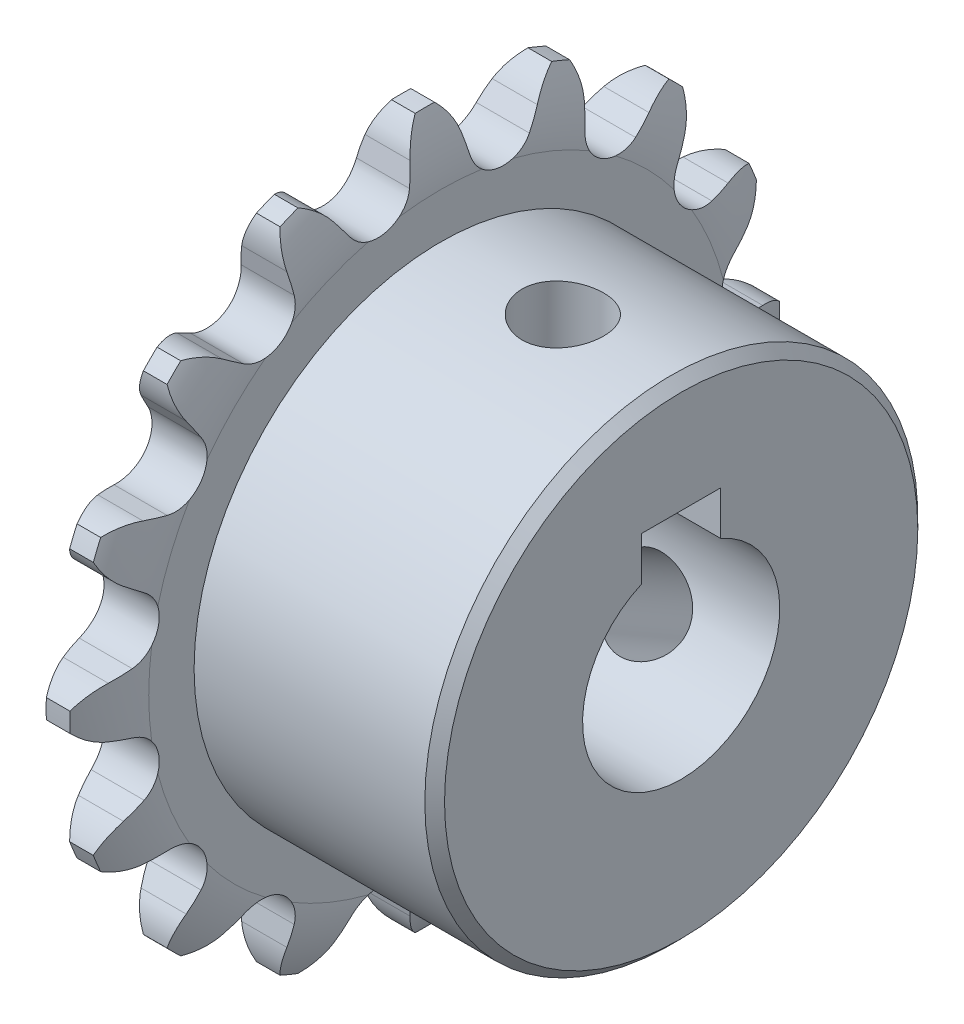
SolidWorks part; units mm, degrees
ref_plane "Front Plane" through (0, 0, 0) normal (0, 0, 1) x (1, 0, 0)
ref_plane "Top Plane" through (0, 0, 0) normal (0, 1, 0) x (1, 0, 0)
ref_plane "Right Plane" through (0, 0, 0) normal (1, 0, 0) x (0, 0, -1)
ref_axis "Axis_X" through (-0.8516, 0, 0) along (1, 0, 0)
ref_axis "Axis_Y" through (0, 19.8, 0) along (0, -1, 0)
ref_axis "Axis_Z" through (0, 0, -19.8) along (0, 0, 1)
sketch "Sketch1" plane through (0, 0, 0) normal (0, 0, 1) x (1, 0, 0)
  line L0 (0, 0) -> (15, 0) construction
  line L1 (0, 5) -> (0, 18)
  line L2 (0, 18) -> (2.8, 18)
  line L3 (2.8, 18) -> (2.8, 12.5)
  line L4 (2.8, 12.5) -> (15, 12.5)
  line L5 (15, 12.5) -> (15, 5)
  line L7 (0, 5) -> (15, 5)
  dimension "Do" = 36
  dimension "H" = 25
  dimension "FIX_1" = 2.8
  dimension "L" = 15
  dimension "D" = 10
revolve "Revolve1" add sketch "Sketch1" angle 360 about axis through (-0.8516, 0, 0) along (1, 0, 0)
sketch "Sketch2" plane through (0, 0, 0) normal (0, 0, 1) x (1, 0, 0)
  line L0 (0, 0) -> (15, 0) construction
  line L1 (0.8, 18) -> (0, 18)
  line L2 (0, 18) -> (0, -18) construction
  line L3 (0, 18) -> (0, 14.8)
  line L4 (15, -12.5) -> (15, 12.5) construction
  line L5 (0, 18) -> (2.8, 18) construction
  line L6 (0, 5) -> (0, 18) construction
  line L7 (2, 18) -> (2.8, 18)
  line L8 (2.8, 18) -> (2.8, 14.8)
  line L9 (2.8, 18) -> (2.8, 12.5) construction
  arc A0 (0, 14.8) -> (0.8, 18) centre (6.8, 14.8) cw
  arc A1 (2.8, 14.8) -> (2, 18) centre (-4, 14.8) ccw
  dimension "FIX_3" = 6.8
  dimension "FIX_4" = 3.2
revolve "Cut-Revolve1" cut sketch "Sketch2" angle 360 about axis through (-0.8516, 0, 0) along (1, 0, 0) reverse direction yes
sketch "Sketch3" plane through (0, 0, 0) normal (0, 0, 1) x (1, 0, 0)
  line L0 (15, 12.5) -> (14.5, 12.5)
  line L1 (14.5, 12.5) -> (15, 12)
  line L2 (15, -12.5) -> (15, 12.5) construction
  line L3 (15, 12) -> (15, 12.5)
  line L4 (0, 0) -> (15, 0) construction
  line L6 (2.8, 12.5) -> (15, 12.5) construction
  dimension "FIX_6" = 45
  dimension "FIX_8" = 0.5
revolve "Cut-Revolve2" cut sketch "Sketch3" angle 360 about axis through (-0.8516, 0, 0) along (1, 0, 0)
ref_plane "Plane1" through (0, 12.5, 0) normal (0, 1, 0) x (1, 0, 0)
hole_wizard "Tap1" positions "Sketch5" profile "Sketch4" hole size "M6x1.0" standard "JIS" end condition up to next
sketch "Sketch5" plane through (0, 12.5, 0) normal (0, 1, 0) x (1, 0, 0)
  line L0 (0, 0) -> (15, 0) construction
  line L1 (15, -12) -> (15, 12) construction
  point P0 (9, 0)
  dimension "L_s" = 6
sketch "Sketch4" plane through (9, 12.5, 0) normal (1, 0, 0) x (0, 0, 1)
  line L0 (0, 0) -> (0, 7.5)
  line L1 (0, 7.5) -> (2.067, 7.5)
  line L2 (2.067, 7.5) -> (2.067, 0)
  line L5 (2.067, 0) -> (0, 0)
  line L11 (0, -6.35) -> (0, 107.95) construction
  dimension "Thru Hole Depth" = 7.5
  dimension "HSD_1" = 4.134
ref_plane "Plane2" through (0, 0, 0) normal (0, -0.5, -0.866) x (1, 0, 0)
ref_plane "Plane3" through (0, -6.25, -10.8253) normal (0, -0.5, -0.866) x (1, 0, 0)
hole_wizard "Tap2" positions "Sketch7" profile "Sketch6" hole size "M6x1.0" standard "JIS" end condition up to next
sketch "Sketch7" plane through (0, -6.25, -10.8253) normal (0, -0.5, -0.866) x (1, 0, 0)
  line L0 (0, 0) -> (15, 0) construction
  line L1 (15, -12) -> (15, 12) construction
  point P0 (9, 0)
  dimension "L_s" = 6
sketch "Sketch6" plane through (9, -6.25, -10.8253) normal (1, 0, 0) x (0, 0.866, -0.5)
  line L0 (0, 0) -> (0, 7.5)
  line L1 (0, 7.5) -> (2.067, 7.5)
  line L2 (2.067, 7.5) -> (2.067, 0)
  line L5 (2.067, 0) -> (0, 0)
  line L11 (0, -6.35) -> (0, 107.95) construction
  dimension "Thru Hole Depth" = 7.5
  dimension "HSD_1" = 4.134
sketch "Sketch8" plane through (15, 0, 0) normal (1, 0, 0) x (0, 0, -1)
  line L0 (0, 0) -> (0, 5) construction
  line L1 (-2, 6.8) -> (2, 6.8)
  line L2 (-2, 6.8) -> (-2, 0)
  line L3 (-2, 0) -> (2, 0)
  line L4 (2, 6.8) -> (2, 0)
  circle A1 centre (0, 0) radius 5 construction
  dimension "B2_s" = 4
  dimension "T2_s" = 1.8
extrude "Cut-Extrude1" cut sketch "Sketch8" against normal through all
sketch "Sketch9" plane through (0, 0, 0) normal (1, 0, 0) x (0, 0, -1)
  line L0 (0, 0) -> (0, 18) construction
  line L1 (0, 0) -> (18, 0) construction
  line L2 (3.1751, 15.9623) -> (4.8388, 15.6314) construction
  line L3 (3.1751, 15.9623) -> (8.4439, 18.7051) construction
  line L4 (0, 0) -> (3.5116, 17.6541) construction
  line L5 (8.4439, 18.7051) -> (2.0458, 17.2279) construction
  line L6 (3.1751, 15.9623) -> (-1.4449, 15.9623) construction
  line L7 (5.1595, 15.8234) -> (4.556, 14.9773)
  line L8 (1.2885, 16.5933) -> (1.5223, 15.5807)
  circle A0 centre (0, 0) radius 18 construction
  arc A1 (1.5223, 15.5807) -> (4.556, 14.9773) centre (3.1751, 15.9623) ccw
  arc A2 (0.4902, 17.9933) -> (1.2885, 16.5933) centre (-1.4449, 15.9623) cw
  circle A3 centre (0, 0) radius 16.275 construction
  arc A4 (6.4328, 16.8113) -> (0.4902, 17.9933) centre (0, 0) ccw
  arc A5 (6.4328, 16.8113) -> (5.1595, 15.8234) centre (7.4434, 14.1943) ccw
  dimension "Dp" = 32.55
  dimension "FIX_11" = 3.3925
  dimension "FIX_12" = 5.94
  dimension "FIX_13" = 4.62
  dimension "KSS_3" = 11.25
  dimension "KSS_5" = 14.5
  dimension "KSS_4" = 38.75
extrude "Cut-Extrude2" cut sketch "Sketch9" along normal up to next
pattern_circular "CirPattern1" count 16 over 360 about axis through (-0.8516, 0, 0) along (1, 0, 0) of "Cut-Extrude2" reverse direction yes
equation "\"Factor\"= 1.082532"
equation "\"KSS_3@Sketch3\" = \"FIX_7@Sketch3\" +  8.128"
equation "\"T\"=16.000000"
equation "\"KSS_3\"= 180 / \"T\""
equation "\"KSS_1\"= \"H@Sketch1\" / 2"
equation "\"KSS_2\"= \"H@Sketch1\" / 2"
equation "\"KSS_4\"= 35 + 60 / \"T\""
equation "\"KSS_5\"= 18 - 56 / \"T\""
